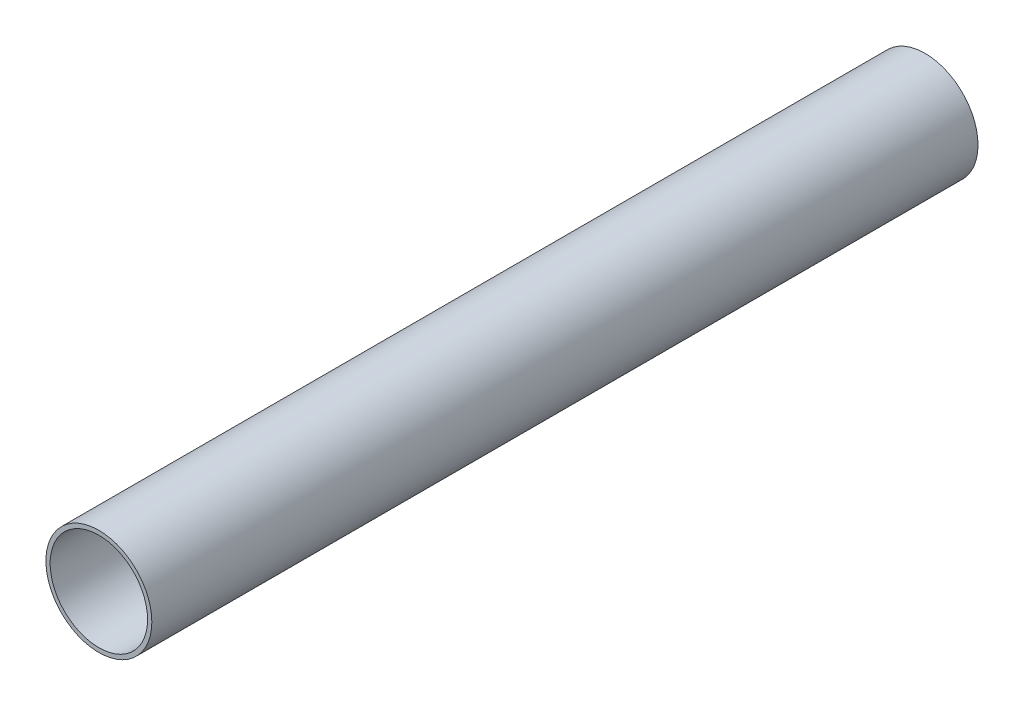
SolidWorks part; units mm, degrees
material "Thornel Mat VMA"
ref_plane "前视基准面" through (0, 0, 0) normal (0, 0, 1) x (1, 0, 0)
ref_plane "上视基准面" through (0, 0, 0) normal (0, 1, 0) x (1, 0, 0)
ref_plane "右视基准面" through (0, 0, 0) normal (1, 0, 0) x (0, 0, -1)
sketch "草图1" plane through (0, 0, 0) normal (0, 0, 1) x (1, 0, 0)
  circle A0 centre (0, 0) radius 11.5
  circle A1 centre (0, 0) radius 12.5
  dimension "D1" = 25
  dimension "D2" = 1
extrude "凸台-拉伸1" add sketch "草图1" along normal blind 195
